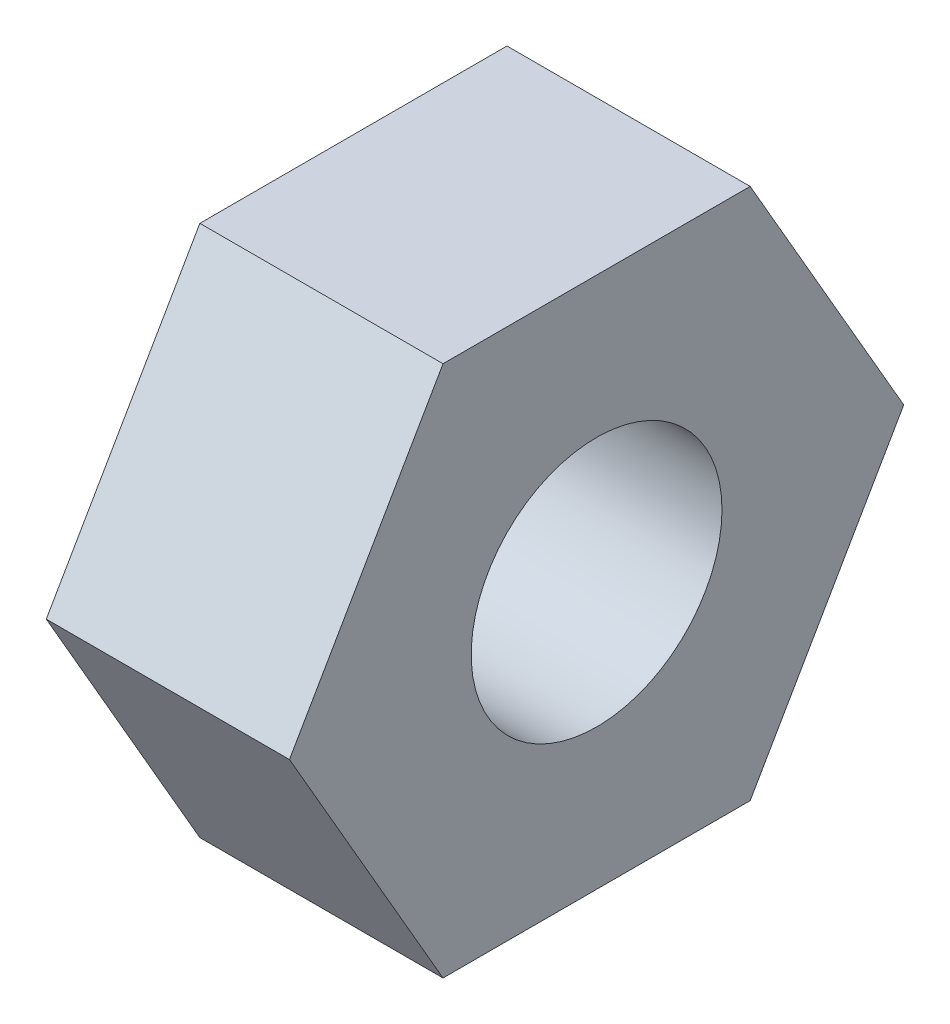
SolidWorks part; units mm, degrees
ref_plane "Front Plane" through (0, 0, 0) normal (0, 0, 1) x (1, 0, 0)
ref_plane "Top Plane" through (0, 0, 0) normal (0, 1, 0) x (1, 0, 0)
ref_plane "Right Plane" through (0, 0, 0) normal (1, 0, 0) x (0, 0, -1)
sketch "Nut Sketch" plane through (0, 0, 0) normal (1, 0, 0) x (0, 0, -1)
  line L0 (4.0415, 0) -> (2.0207, 3.5)
  line L1 (2.0207, 3.5) -> (-2.0207, 3.5)
  line L2 (-2.0207, 3.5) -> (-4.0415, 0)
  line L3 (-4.0415, 0) -> (-2.0207, -3.5)
  line L4 (-2.0207, -3.5) -> (2.0207, -3.5)
  line L5 (2.0207, -3.5) -> (4.0415, 0)
extrude "Nut" add sketch "Nut Sketch" along normal blind 3.2
ref_axis "Engine Axis" through (3.36, 0, 0) along (-1, 0, 0)
sketch "Thread Sketch" plane through (0, 0, 0) normal (0, 0, 1) x (1, 0, 0)
  line L0 (-1000, 0) -> (1000, 0) construction
  line L1 (-1, 0) -> (4.2, 0)
  line L2 (4.2, 0) -> (4.2, 1.65)
  line L3 (4.2, 1.65) -> (-1, 1.65)
  line L4 (-1, 1.65) -> (-1, 0)
revolve "Thread" cut sketch "Thread Sketch" angle 360 about L0
